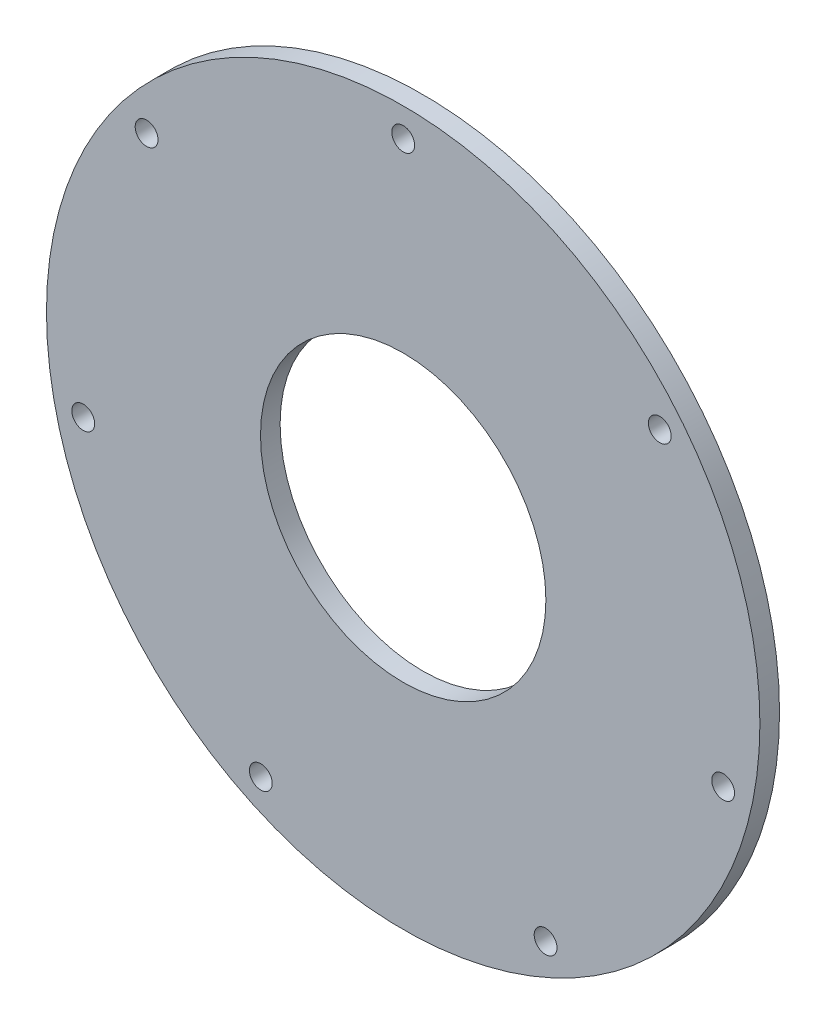
SolidWorks part; units mm, degrees
ref_plane "Ebene vorne" through (0, 0, 0) normal (0, 0, 1) x (1, 0, 0)
ref_plane "Ebene oben" through (0, 0, 0) normal (0, 1, 0) x (1, 0, 0)
ref_plane "Ebene rechts" through (0, 0, 0) normal (1, 0, 0) x (0, 0, -1)
sketch "Skizze1" plane through (0, 0, 0) normal (0, 0, 1) x (1, 0, 0)
  circle A0 centre (0, 0) radius 50
  circle A1 centre (0, 0) radius 20
  dimension "D1" = 100
  dimension "D2" = 40
extrude "Aufsatz-Linear austragen1" add sketch "Skizze1" along normal blind 2.75
hole_wizard "Ø3.2 (3.2) Durchmesser Bohrung1" positions "Skizze2" profile "Skizze3" hole size "Ø3.2" standard "ISO" end condition through all
sketch "Skizze2" plane through (0, 0, 2.75) normal (0, 0, 1) x (1, 0, 0)
  line L0 (0, 0) -> (0, -50000) construction
  circle A0 centre (0, 0) radius 46 construction
  circle A1 centre (0.0005, 0.0009) radius 46 construction
  circle A2 centre (0, 0.0017) radius 46 construction
  circle A3 centre (-0.001, 0.0017) radius 46 construction
  circle A4 centre (-0.0015, 0.0009) radius 46 construction
  circle A5 centre (-0.001, 0) radius 46 construction
  point P8 (0, 46)
  point P48 (0, 0)
  point P50 (0, 0)
  point P52 (0, 0)
  point P54 (0, 0)
  point P56 (0, 0)
  dimension "D1" = 92
  dimension "D2" = 6
sketch "Skizze3" plane through (0, 46, 2.75) normal (1, 0, 0) x (0, -1, 0)
  line L0 (0, 0) -> (0, 2.75)
  line L1 (0, 2.75) -> (1.6, 2.75)
  line L2 (1.6, 2.75) -> (1.6, 0)
  line L5 (1.6, 0) -> (0, 0)
  line L11 (0, -6.35) -> (0, 107.95) construction
  dimension "Bohrerdurchmesser" = 3.2
  dimension "Bohrungstiefe" = 2.75
pattern_circular "Kreismuster1" count 7 over 360 about axis through (0, 0, 2.75) along (0, 0, 1) of "Ø3.2 (3.2) Durchmesser Bohrung1"
